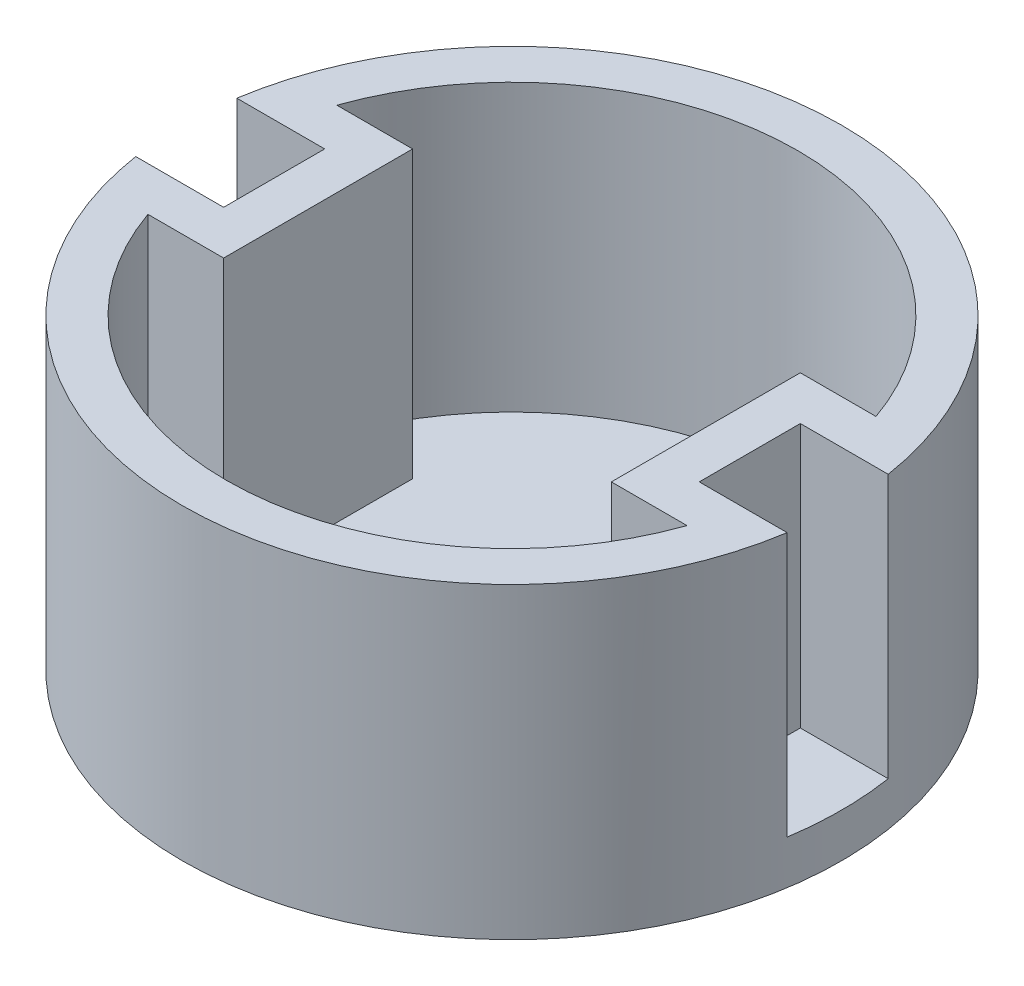
SolidWorks part; units mm, degrees
ref_plane "Front Plane" through (0, 0, 0) normal (0, 0, 1) x (1, 0, 0)
ref_plane "Top Plane" through (0, 0, 0) normal (0, 1, 0) x (1, 0, 0)
ref_plane "Right Plane" through (0, 0, 0) normal (1, 0, 0) x (0, 0, -1)
sketch "Sketch1" plane through (0, 0, 0) normal (0, 1, 0) x (1, 0, 0)
  circle A0 centre (-19.1438, 2.8512) radius 75
  dimension "D1" = 150
extrude "Boss-Extrude1" add sketch "Sketch1" along normal blind 70
sketch "Sketch3" plane through (0, 70, 0) normal (0, 1, 0) x (1, 0, 0)
  line L0 (54.9693, 14.3512) -> (54.9693, -8.6488)
  line L1 (-93.2568, 14.3512) -> (-73.2568, 14.3512)
  line L2 (-93.2568, 14.3512) -> (-93.2568, -8.6488)
  line L3 (-93.2568, -8.6488) -> (-73.2568, -8.6488)
  line L4 (-73.2568, 14.3512) -> (-73.2568, -8.6488)
  line L5 (54.9693, 14.3512) -> (34.9693, 14.3512)
  line L6 (54.9693, 14.3512) -> (54.9693, -8.6488)
  line L7 (54.9693, -8.6488) -> (34.9693, -8.6488)
  line L8 (34.9693, 14.3512) -> (34.9693, -8.6488)
  line L9 (54.9693, 14.3512) -> (56.9615, 14.3512)
  line L10 (54.9693, -8.6488) -> (56.9615, -8.6488)
  line L11 (56.9615, 14.3512) -> (56.9615, -8.6488)
  line L12 (-93.2568, 14.3512) -> (-93.2568, -8.6488)
  line L13 (-93.2568, 14.3512) -> (-96.1499, 14.3512)
  line L14 (-93.2568, -8.6488) -> (-96.1499, -8.6488)
  line L15 (-96.1499, 14.3512) -> (-96.1499, -8.6488)
  circle A0 centre (-19.1438, 2.8512) radius 65
  circle A1 centre (-19.1438, 2.8512) radius 75 construction
  dimension "D1" = 130
  dimension "D2" = 20
  dimension "D3" = 23
extrude "Cut-Extrude1" cut sketch "Sketch3" against normal blind 65 contours L5 A0 L1 L4 L3 L7 L8 region at (-19.1438, 70, -2.8512)
extrude "Cut-Extrude3" cut sketch "Sketch3<3>" against normal blind 60 contours L7 A0 L5 L8 | L1 A0 L3 L4 | L12 L13 L15 L14 | L2 L1 L4 L3 | L6 L5 L8 L7 | L0 L9 L11 L10 region at (40.2468, 70, -2.8512) region at (-78.5344, 70, -2.8512)
sketch "Sketch3<3>" plane through (0, 70, 0) normal (0, 1, 0) x (1, 0, 0) same geometry as "Sketch3"
sketch "Sketch6" plane through (0, 5, 0) normal (0, 1, 0) x (1, 0, 0)
  line L0 (-83.1184, 14.3512) -> (-73.2568, 14.3512)
  line L1 (-83.1184, 14.3512) -> (-83.1184, 24.3512)
  line L2 (-73.2568, 14.3512) -> (-73.2568, 24.3512)
  line L3 (-83.1184, 24.3512) -> (-73.2568, 24.3512)
  line L4 (-83.1184, -8.6488) -> (-73.2568, -8.6488)
  line L5 (-83.1184, -8.6488) -> (-83.1184, -18.6488)
  line L6 (-73.2568, -8.6488) -> (-73.2568, -18.6488)
  line L7 (-83.1184, -18.6488) -> (-73.2568, -18.6488)
  line L8 (-73.2568, 24.3512) -> (-73.2568, -18.6488)
  line L9 (-73.2568, 24.3512) -> (-63.2568, 24.3512)
  line L10 (-73.2568, -18.6488) -> (-63.2568, -18.6488)
  line L11 (-63.2568, 24.3512) -> (-63.2568, -18.6488)
  line L12 (44.8308, 14.3512) -> (34.9693, 14.3512)
  line L13 (44.8308, 14.3512) -> (44.8308, 24.3512)
  line L14 (34.9693, 14.3512) -> (34.9693, 24.3512)
  line L15 (44.8308, 24.3512) -> (34.9693, 24.3512)
  line L16 (34.9693, -8.6488) -> (44.8308, -8.6488)
  line L17 (34.9693, -8.6488) -> (34.9693, -18.6488)
  line L18 (44.8308, -8.6488) -> (44.8308, -18.6488)
  line L19 (34.9693, -18.6488) -> (44.8308, -18.6488)
  line L20 (34.9693, 24.3512) -> (34.9693, -18.6488)
  line L21 (34.9693, 24.3512) -> (24.9693, 24.3512)
  line L22 (34.9693, -18.6488) -> (24.9693, -18.6488)
  line L23 (24.9693, 24.3512) -> (24.9693, -18.6488)
  line M12 (34.9693, 14.3512) -> (44.8308, 14.3512)
  arc M13 (44.8308, 14.3512) -> (-83.1184, 14.3512) centre (-19.1438, 2.8512) ccw
  line M14 (-83.1184, 14.3512) -> (-73.2568, 14.3512)
  line M15 (-73.2568, 14.3512) -> (-73.2568, -8.6488)
  line M16 (-73.2568, -8.6488) -> (-83.1184, -8.6488)
  arc M17 (-83.1184, -8.6488) -> (44.8308, -8.6488) centre (-19.1438, 2.8512) ccw
  line M18 (44.8308, -8.6488) -> (34.9693, -8.6488)
  line M19 (34.9693, -8.6488) -> (34.9693, 14.3512)
  dimension "D1" = 10
  dimension "D2" = 10
  dimension "D3" = 10
  dimension "D4" = 10
  dimension "D5" = 10
  dimension "D6" = 10
extrude "Boss-Extrude2" add sketch "Sketch6" along normal blind 65 contours L3 L2 M13 M14 | L11 L9 L2 L6 L10 M15 | L7 L6 M17 M16 | L21 L23 L22 L17 L14 M19 | L17 L19 M17 M18 | L15 L14 M13 M12 region at (-77.6337, 5, -19.0989) region at (-68.2568, 5, -2.8512) region at (-77.6337, 5, 13.3965) region at (39.3462, 5, -19.0989) region at (29.9693, 5, -2.8512) region at (39.3462, 5, 13.3965)
